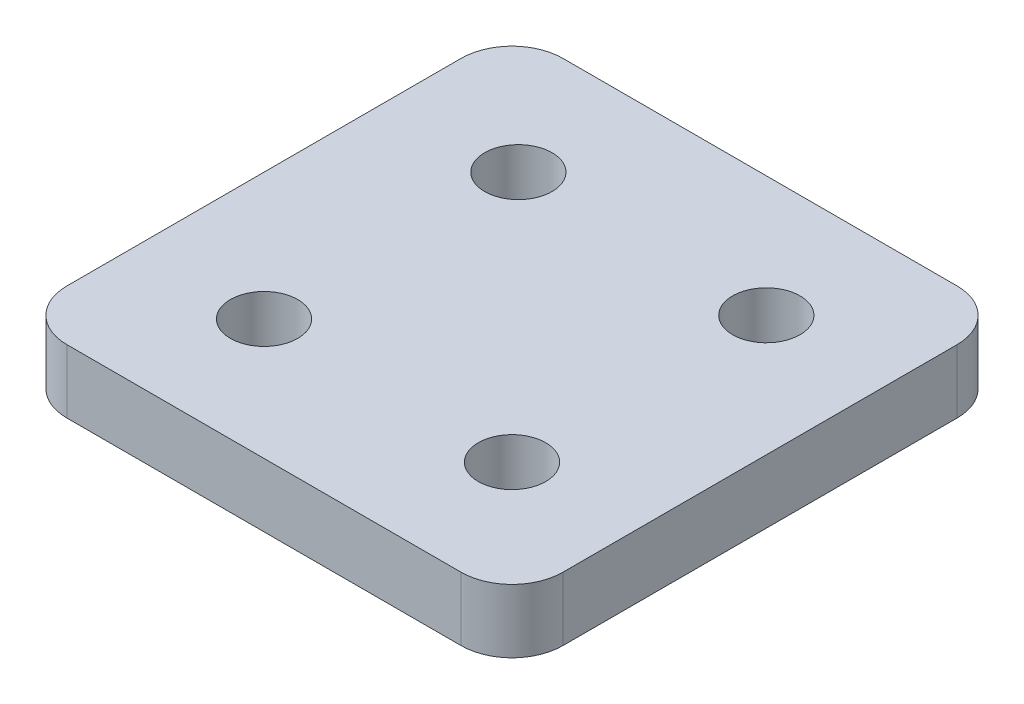
SolidWorks part; units mm, degrees
ref_plane "Top" through (0, 0, 0) normal (0, 0, 1) x (1, 0, 0)
ref_plane "Front" through (0, 0, 0) normal (0, 1, 0) x (1, 0, 0)
ref_plane "Right" through (0, 0, 0) normal (1, 0, 0) x (0, 0, -1)
sketch "2 Hole Profile Sketch" [suppressed] plane through (0, 0, 0) normal (0, 1, 0) x (1, 0, 0)
  line L0 (0, -10) -> (0, 10) construction
  line L1 (-16.5, -9.5) -> (16.5, -9.5)
  line L2 (-19.5, -6.5) -> (-19.5, 6.5)
  line L3 (-16.5, 9.5) -> (16.5, 9.5)
  line L4 (19.5, -6.5) -> (19.5, 6.5)
  line L5 (-20, -10) -> (20, -10) construction
  line L6 (-20, -10) -> (-20, 10) construction
  line L7 (-20, 10) -> (20, 10) construction
  line L8 (20, -10) -> (20, 10) construction
  arc A0 (-16.5, -9.5) -> (-19.5, -6.5) centre (-16.5, -6.5) cw
  arc A1 (-16.5, 9.5) -> (-19.5, 6.5) centre (-16.5, 6.5) ccw
  arc A2 (19.5, 6.5) -> (16.5, 9.5) centre (16.5, 6.5) ccw
  arc A3 (16.5, -9.5) -> (19.5, -6.5) centre (16.5, -6.5) ccw
  circle A4 centre (-10, 0) radius 2.65
  circle A5 centre (10, 0) radius 2.65
  point P24 (0, 0)
  dimension "D2" = 0.5
  dimension "D3" = 0.5
  dimension "D4" = 0.5
  dimension "D7" = 10
  dimension "D1" = 3
  dimension "D5" = 0.5
  dimension "D6" = 20
  dimension "D9" = 10
  dimension "D12" = 20
  dimension "D8" = 5.3
  dimension "D11" = 20
extrude "2 Hole Profile" [suppressed] add sketch "2 Hole Profile Sketch" along normal blind 5
sketch "3 Hole Profile Sketch" [suppressed] plane through (0, 0, 0) normal (0, 1, 0) x (1, 0, 0)
  line L0 (0, -10) -> (0, 10) construction
  line L1 (-16.5, -9.5) -> (36.5, -9.5)
  line L2 (-19.5, -6.5) -> (-19.5, 6.5)
  line L3 (-16.5, 9.5) -> (36.5, 9.5)
  line L4 (39.5, -6.5) -> (39.5, 6.5)
  line L5 (-20, -10) -> (40, -10) construction
  line L6 (-20, -10) -> (-20, 10) construction
  line L7 (-20, 10) -> (40, 10) construction
  line L8 (40, -10) -> (40, 10) construction
  arc A0 (-16.5, -9.5) -> (-19.5, -6.5) centre (-16.5, -6.5) cw
  arc A1 (-16.5, 9.5) -> (-19.5, 6.5) centre (-16.5, 6.5) ccw
  arc A2 (39.5, 6.5) -> (36.5, 9.5) centre (36.5, 6.5) ccw
  arc A3 (36.5, -9.5) -> (39.5, -6.5) centre (36.5, -6.5) ccw
  circle A4 centre (-10, 0) radius 2.65
  circle A5 centre (10, 0) radius 2.65
  circle A6 centre (30, 0) radius 2.65
  point P29 (0, 0)
  dimension "D2" = 0.5
  dimension "D3" = 0.5
  dimension "D4" = 0.5
  dimension "D10" = 20
  dimension "D7" = 10
  dimension "D1" = 3
  dimension "D8" = 5.3
  dimension "D5" = 0.5
  dimension "D6" = 20
  dimension "D9" = 10
  dimension "D11" = 40
  dimension "D12" = 20
extrude "3 Hole Thickness Extrude" [suppressed] add sketch "3 Hole Profile Sketch" along normal blind 5
sketch "4 Hole Profile Sketch" plane through (0, 0, 0) normal (0, 1, 0) x (1, 0, 0)
  line L1 (-15.5, -19.5) -> (15.5, -19.5)
  line L2 (-19.5, -15.5) -> (-19.5, 15.5)
  line L3 (-15.5, 19.5) -> (15.5, 19.5)
  line L4 (19.5, -15.5) -> (19.5, 15.5)
  line L5 (0, 19.5) -> (0, -19.5) construction
  line L6 (-19.5, 0) -> (19.5, 0) construction
  line L7 (-20, 20) -> (20, 20) construction
  line L8 (-20, 20) -> (-20, -20) construction
  line L9 (-20, -20) -> (20, -20) construction
  line L10 (20, 20) -> (20, -20) construction
  line L11 (-20, 20) -> (20, -20) construction
  line L12 (-20, -20) -> (20, 20) construction
  circle A0 centre (10, -10) radius 2.65
  circle A1 centre (10, 10) radius 2.65
  circle A2 centre (-9.5, -10) radius 2.65
  circle A3 centre (-9.5, 10) radius 2.65
  arc A4 (-19.5, -15.5) -> (-15.5, -19.5) centre (-15.5, -15.5) ccw
  arc A5 (19.5, -15.5) -> (15.5, -19.5) centre (15.5, -15.5) cw
  arc A6 (15.5, 19.5) -> (19.5, 15.5) centre (15.5, 15.5) cw
  arc A7 (-19.5, 15.5) -> (-15.5, 19.5) centre (-15.5, 15.5) cw
  point P14 (0, 0)
  point P22 (-25, -26)
  point P144 (0, 0)
  dimension "Corner Radius" = 4
  dimension "D9" = 5.3
  dimension "D5" = 10
  dimension "D6" = 10
  dimension "D7" = 10
  dimension "D8" = 10
  dimension "D1" = 40
  dimension "D2" = 0.5
  dimension "D3" = 0.5
  dimension "D4" = 0.5
  dimension "D10" = 20
extrude "4 Hole Thickness Extrude" add sketch "4 Hole Profile Sketch" along normal blind 5
sketch "6 Hole Extension Sketch" plane through (0, 0, 0) normal (0, 1, 0) x (1, 0, 0)
  line L0 (39.5, -15.5) -> (39.5, 15.5)
  line L1 (-20, -19.5) -> (15.5, -19.5) construction
  line L2 (-20, -19.5) -> (-20, 19.5) construction
  line L3 (-20, 19.5) -> (15.5, 19.5) construction
  line L4 (19.5, -15.5) -> (19.5, 15.5)
  line L5 (0, 19.5) -> (0, -19.5) construction
  line L6 (-20, 0) -> (19.5, 0) construction
  line L7 (15.5, -19.5) -> (35.5, -19.5)
  line L8 (15.5, 19.5) -> (35.5, 19.5)
  arc A8 (39.5, -15.5) -> (35.5, -19.5) centre (35.5, -15.5) cw
  arc A9 (35.5, 19.5) -> (39.5, 15.5) centre (35.5, 15.5) cw
  arc A10 (19.5, -15.5) -> (15.5, -19.5) centre (15.5, -15.5) cw
  arc A11 (19.5, 15.5) -> (15.5, 19.5) centre (15.5, 15.5) ccw
  circle A12 centre (29.5, -10) radius 2.65
  circle A13 centre (29.5, 10) radius 2.65
  point P18 (-22.5, -23)
  point P27 (0, 0)
  dimension "Corner Radius" = 4
  dimension "D5" = 5.3
  dimension "D1" = 19.5
  dimension "D2" = 20
  dimension "D6" = 39
  dimension "D3" = 10
  dimension "D4" = 10
  dimension "D7" = 10
  dimension "D8" = 20
extrude "6 Hole Extension Extrude" [suppressed] add sketch "6 Hole Extension Sketch" along normal up to surface (5 mm away) up to face at (-9.5, 5, 12.65)
equation "\"M5 Close Fit Hole\"= 5.3mm"
equation "\"D9@4 Hole Profile Sketch\" = \"M5 Close Fit Hole\""
equation "\"D5@6 Hole Extension Sketch\" = \"M5 Close Fit Hole\""
equation "\"Clearance\"= 0.5mm"
equation "\"D2@4 Hole Profile Sketch\"=\"Clearance\""
equation "\"D3@4 Hole Profile Sketch\"=\"Clearance\""
equation "\"D4@4 Hole Profile Sketch\"=\"Clearance\""
equation "\"D6@6 Hole Extension Sketch\"=40-2*\"Clearance\""
equation "\"D1@6 Hole Extension Sketch\"=20-\"Clearance\""
equation "\"D2@3 Hole Profile Sketch\" = \"Clearance\""
equation "\"D3@3 Hole Profile Sketch\" = \"Clearance\""
equation "\"D4@3 Hole Profile Sketch\" = \"Clearance\""
equation "\"D5@3 Hole Profile Sketch\" = \"Clearance\""
equation "\"D8@3 Hole Profile Sketch\" = \"M5 Close Fit Hole\""
equation "\"Plate Thickness\"= 5"
equation "\"D1@4 Hole Thickness Extrude\"=\"Plate Thickness\""
equation "\"D1@3 Hole Thickness Extrude\"=\"Plate Thickness\""
equation "\"D8@2 Hole Profile Sketch\" = \"M5 Close Fit Hole\""
equation "\"D1@2 Hole Profile\"=\"Plate Thickness\""
